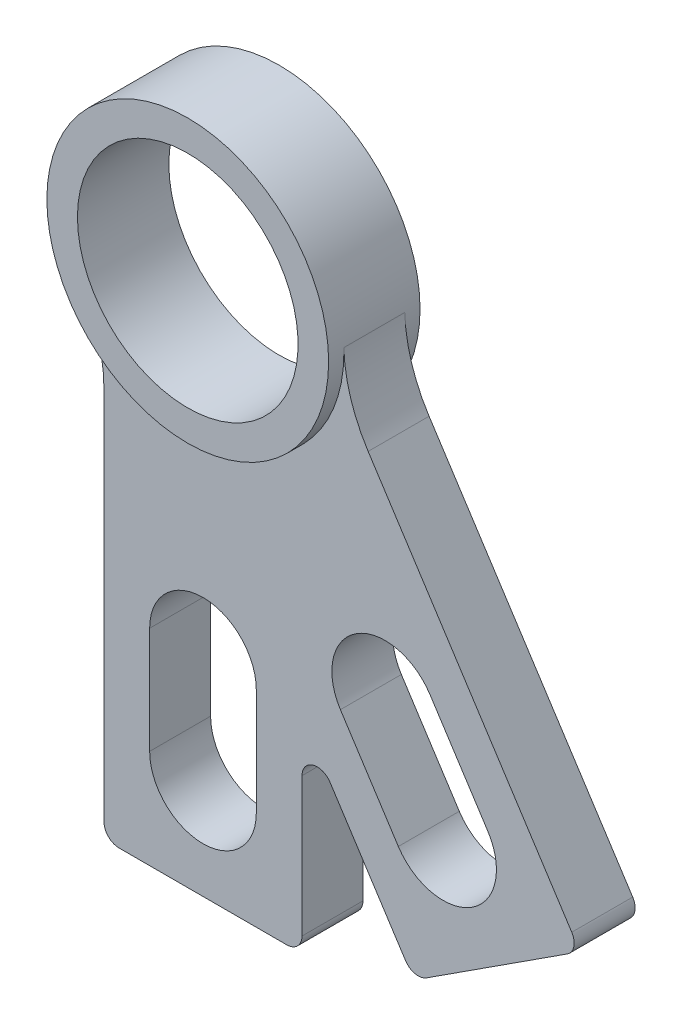
SolidWorks part; units mm, degrees
material "AISI 4130 Steel, annealed at 865C"
ref_plane "X-Y Datum" through (0, 0, 0) normal (0, 0, 1) x (1, 0, 0)
ref_plane "X-Z Datum" through (0, 0, 0) normal (0, 1, 0) x (1, 0, 0)
ref_plane "Y-Z Datum" through (0, 0, 0) normal (1, 0, 0) x (0, 0, -1)
sketch "Sketch1" plane through (0, 0, 0) normal (0, 0, 1) x (1, 0, 0)
  line L0 (0, -46.0556) -> (0, -34.9431) construction
  line L1 (-5.5562, -46.0556) -> (-5.5562, -34.9431)
  line L2 (5.5562, -46.0556) -> (5.5562, -34.9431)
  line L3 (25.0228, -38.6649) -> (18.9852, -29.3357) construction
  line L4 (20.3582, -41.6837) -> (14.3206, -32.3545)
  line L5 (29.6874, -35.6461) -> (23.6498, -26.3169)
  line L6 (-10.3187, -15.7343) -> (-10.3187, -56.3743)
  line L7 (-10.3187, -56.3743) -> (10.3187, -56.3743)
  line L10 (21.9663, -52.9341) -> (39.292, -41.7214)
  line L11 (39.292, -41.7214) -> (17.2116, -7.603)
  line L14 (0, -51.6118) -> (0, -56.3743) construction
  line L15 (28.0416, -43.3295) -> (30.6292, -47.3278) construction
  line L16 (26.6686, -30.9815) -> (30.6669, -28.3939) construction
  line L17 (-5.5562, -40.4993) -> (-10.3187, -40.4993) construction
  line L18 (-10.3187, -24.6243) -> (10.3187, -24.6243) construction
  line L19 (10.3187, -24.6243) -> (10.3187, -56.3743) construction
  line L20 (5.5562, -40.4993) -> (10.3187, -40.4993) construction
  line L21 (0, -29.3868) -> (0, -24.6243) construction
  line L22 (21.9663, -52.9341) -> (4.716, -26.2791) construction
  line L23 (4.716, -26.2791) -> (22.0417, -15.0664) construction
  line L24 (17.3394, -37.0191) -> (13.3411, -39.6066) construction
  line L25 (15.9664, -24.671) -> (13.3788, -20.6728) construction
  line L30 (21.9663, -52.9341) -> (10.3187, -34.9365)
  line L32 (10.3187, -34.9365) -> (10.3187, -56.3743)
  line L34 (218.5438, -337.6911) -> (0, 0) construction
  line L35 (0, -404.7476) -> (0, 0) construction
  circle A0 centre (0, 0) radius 11.4954
  arc A1 (-5.5562, -46.0556) -> (5.5562, -46.0556) centre (0, -46.0556) ccw
  arc A2 (5.5562, -34.9431) -> (-5.5562, -34.9431) centre (0, -34.9431) ccw
  arc A3 (20.3582, -41.6837) -> (29.6874, -35.6461) centre (25.0228, -38.6649) ccw
  arc A4 (23.6498, -26.3169) -> (14.3206, -32.3545) centre (18.9852, -29.3357) ccw
  arc A5 (14.673, 0.4911) -> (-12.5852, -7.5598) centre (0, 0) ccw
  arc A6 (17.2116, -7.603) -> (14.673, 0.4911) centre (30.5391, 1.0221) cw
  arc A7 (-10.3187, -15.7343) -> (-12.5852, -7.5598) centre (-26.1937, -15.7343) ccw
  arc A14 (-12.5852, -7.5598) -> (14.673, 0.4911) centre (0, 0) ccw
  point P5 (0, -40.4993)
  point P11 (22.004, -34.0003)
  point P24 (30.6292, -47.3278)
  point P31 (0, -56.3743)
  point P36 (0, 0)
  point P39 (28.0416, -43.3295)
  dimension "D1" = 22.9908
  dimension "D2" = 14.6812
  dimension "D8" = 15.875
  dimension "D3" = 20.6375
  dimension "D4" = 4.7625
  dimension "D5" = 31.75
  dimension "D6" = 8.89
  dimension "D7" = 8.89
extrude "Boss-Extrude2" add sketch "Sketch1" along normal mid plane 9.525 contours A5 A14 A0 region at (-4.041, 13.6817, 0)
extrude "Boss-Extrude3" add sketch "Sketch1<4>" along normal mid plane 6.35 contours A14 A7 L6 L7 L10 L11 A6 A4 L5 A3 L4 A2 L2 A1 L1 region at (9.2832, -31.4304, 0)
sketch "Sketch1<4>" plane through (0, 0, 0) normal (0, 0, 1) x (1, 0, 0) same geometry as "Sketch1"
fillet "Fillet1" radius 1.5875 5 edges at (-10.3187, -56.3743, 0) (39.292, -41.7214, 0) (10.3187, -56.3743, 0) (21.9663, -52.9341, 0) (10.3187, -34.9365, 0)
sketch "Sketch2" plane through (0, 0, 4.7625) normal (0, 0, 1) x (1, 0, 0)
  point P0 (0, 0)
sketch "Sketch3" plane through (0, 0, -4.7625) normal (0, 0, -1) x (-1, 0, 0)
  point P0 (0, 0)
